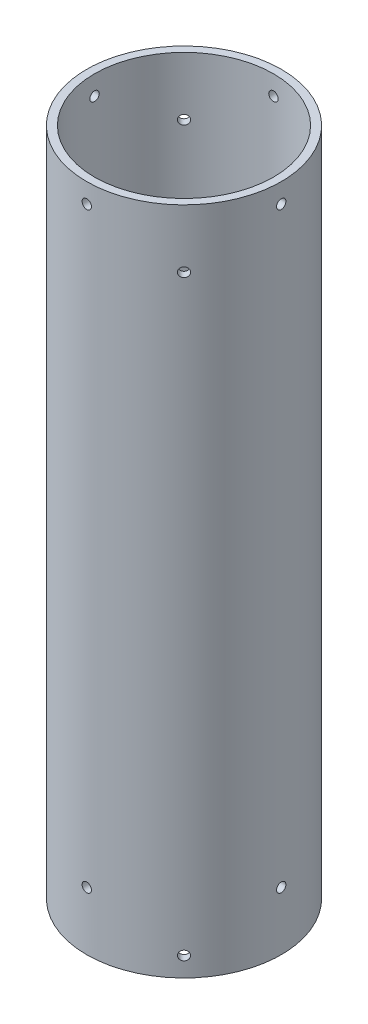
SolidWorks part; units mm, degrees
material "ПВХ 0.007 Смягченный"
ref_plane "Спереди" through (0, 0, 0) normal (0, 0, 1) x (1, 0, 0)
ref_plane "Сверху" through (0, 0, 0) normal (0, 1, 0) x (1, 0, 0)
ref_plane "Справа" through (0, 0, 0) normal (1, 0, 0) x (0, 0, -1)
sketch "Эскиз1" plane through (0, 0, 0) normal (0, 1, 0) x (1, 0, 0)
  circle A0 centre (0, 0) radius 25
  circle A1 centre (0, 0) radius 23
  dimension "ExDBody" = 50
  dimension "InDBody" = 46
extrude "Бобышка-Вытянуть1" add sketch "Эскиз1" along normal blind 172
ref_plane "Плоскость1" through (0, 31, 0) normal (0, -1, 0) x (-1, 0, 0)
sketch "Эскиз3" plane through (0, 0, 0) normal (1, 0, 0) x (0, 0, -1)
  line L0 (23, 172) -> (-23, 172) construction
  line L2 (-25, 0) -> (25, 0) construction
  circle A0 centre (0, 167) radius 1.2
  circle A3 centre (0, 15) radius 1.2
  dimension "D1" = 5
  dimension "D3" = 15
  dimension "D2" = 2.4
  dimension "D4" = 2.4
extrude "Вырез-Вытянуть2" cut sketch "Эскиз3" against normal through all
pattern_circular "Круговой массив1" count 4 over 360 about axis through (0, 172, 0) along (0, -1, 0) of "Вырез-Вытянуть2"
ref_plane "Плоскость2" through (0, 0, 0) normal (-0.7071, 0, 0.7071) x (0, -1, 0)
sketch "Эскиз11" plane through (0, 0, 0) normal (-0.7071, 0, 0.7071) x (0, -1, 0)
  line L0 (-172, 0) -> (0, 0) construction
  line L1 (0, -25) -> (0, 25) construction
  line L2 (-172, 25) -> (-172, -25) construction
  circle A0 centre (-5, 0) radius 1.2
  circle A1 centre (-157, 0) radius 1.2
  dimension "D1" = 2.4
  dimension "D3" = 15
  dimension "D4" = 2.4
  dimension "D2" = 5
extrude "Вырез-Вытянуть10" cut sketch "Эскиз11" against normal through all
pattern_circular "Круговой массив2" count 4 over 360 about axis through (0, 172, 0) along (0, -1, 0) of "Вырез-Вытянуть10"
